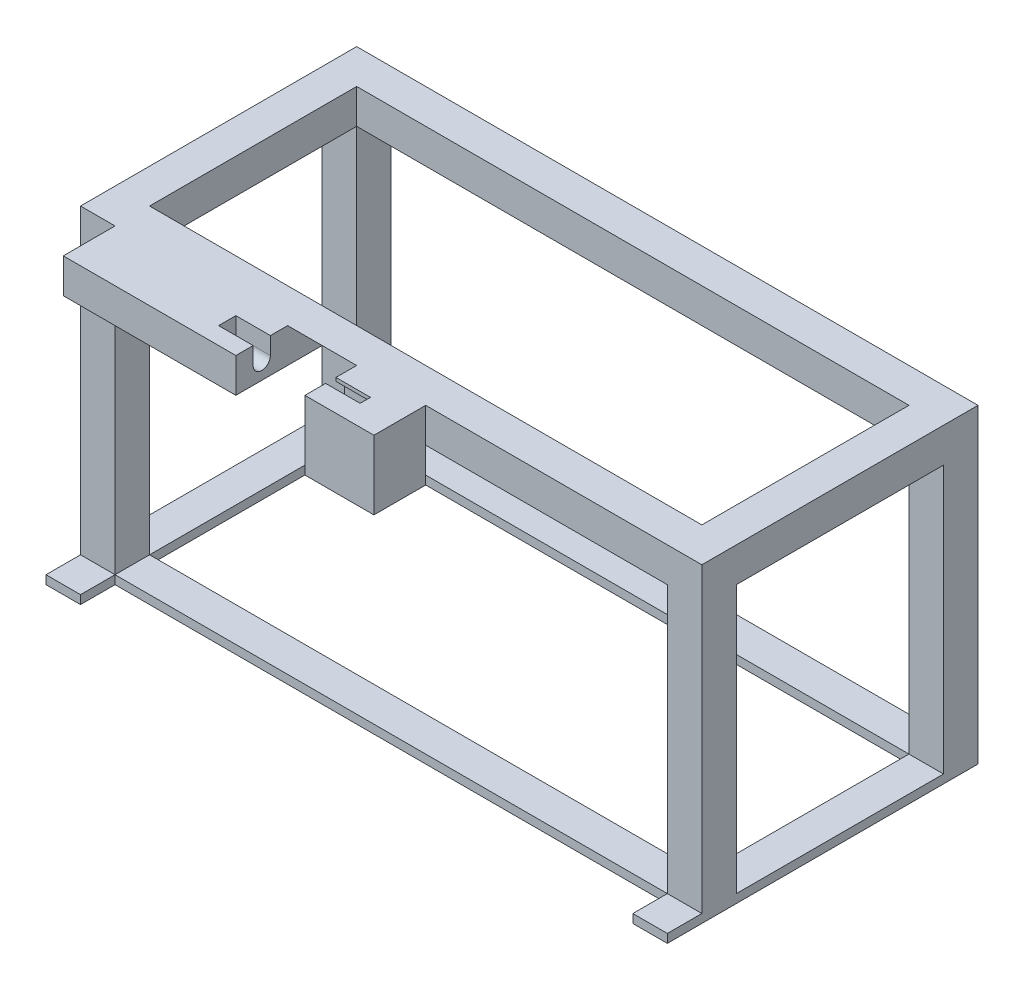
SolidWorks part; units mm, degrees
ref_plane "Front Plane" through (0, 0, 0) normal (0, 0, 1) x (1, 0, 0)
ref_plane "Top Plane" through (0, 0, 0) normal (0, 1, 0) x (1, 0, 0)
ref_plane "Right Plane" through (0, 0, 0) normal (1, 0, 0) x (0, 0, -1)
sketch "Sketch1" plane through (0, 0, 0) normal (0, 1, 0) x (1, 0, 0)
  line L0 (-203.2, 76.2) -> (-203.2, 101.6) construction
  line L1 (-203.2, -76.2) -> (203.2, -76.2)
  line L2 (-203.2, -76.2) -> (-203.2, 76.2)
  line L3 (-203.2, 76.2) -> (203.2, 76.2)
  line L4 (203.2, -76.2) -> (203.2, 76.2)
  line L5 (-203.2, -76.2) -> (203.2, 76.2) construction
  line L6 (-203.2, 76.2) -> (203.2, -76.2) construction
  line L7 (-228.6, -101.6) -> (228.6, -101.6)
  line L8 (-228.6, -101.6) -> (-228.6, 101.6)
  line L9 (-228.6, 101.6) -> (228.6, 101.6)
  line L10 (228.6, -101.6) -> (228.6, 101.6)
  line L11 (-228.6, -101.6) -> (228.6, 101.6) construction
  line L12 (-228.6, 101.6) -> (228.6, -101.6) construction
  line L13 (-203.2, 101.6) -> (-203.2, 76.2)
  line L14 (-203.2, 76.2) -> (-228.6, 76.2)
  line L15 (-228.6, -101.6) -> (-228.6, -127)
  line L16 (-228.6, -127) -> (-203.2, -127)
  line L17 (-203.2, -127) -> (-203.2, -101.6)
  line L18 (0, -125.73) -> (0, 125.73) construction
  line L19 (203.2, -127) -> (203.2, -101.6)
  line L20 (228.6, -127) -> (203.2, -127)
  line L21 (228.6, -101.6) -> (228.6, -127)
  line L22 (-203.2, -76.2) -> (-228.6, -76.2)
  line L23 (-203.2, -76.2) -> (-203.2, -101.6)
  line L24 (203.2, -76.2) -> (203.2, -101.6)
  line L25 (203.2, -76.2) -> (228.6, -76.2)
  line L26 (203.2, 76.2) -> (228.6, 76.2)
  line L27 (203.2, 101.6) -> (203.2, 76.2)
  point P0 (0, 0)
  point P6 (0, 0)
  dimension "D1" = 457.2
  dimension "D2" = 25.4
  dimension "D3" = 152.4
extrude "Boss-Extrude1" add sketch "Sketch1" along normal blind 6.35 separate body contours L23 L22 L8 L7 | L16 L17 L7 L15 | L24 L1 L23 L7 | L25 L24 L7 L10 | L21 L7 L19 L20 | L27 L9 L13 L3 | L22 L2 L14 L8 | L26 L4 L25 L10 region at (-215.9, 0, 0) region at (-215.9, 0, 88.9) region at (0, 0, 88.9) region at (215.9, 0, 88.9) region at (215.9, 0, 0) region at (0, 0, -88.9) region at (-215.9, 0, 114.3) region at (215.9, 0, 114.3)
extrude "Boss-Extrude2" add sketch "Sketch1<4>" along normal blind 228.6 contours L23 L22 L8 L7 | L25 L24 L7 L10 | L9 L27 L26 L10 | L14 L13 L9 L8 region at (-215.9, 0, 88.9) region at (215.9, 0, 88.9) region at (-215.9, 0, -88.9) region at (215.9, 0, -88.9)
sketch "Sketch1<4>" plane through (0, 0, 0) normal (0, 1, 0) x (1, 0, 0) same geometry as "Sketch1"
extrude "Boss-Extrude3" add sketch "Sketch1<5>" along normal blind 25.4 from offset 203.2 contours L27 L9 L13 L3 | L24 L1 L23 L7 | L22 L2 L14 L8 | L26 L4 L25 L10 region at (-215.9, 0, 0) region at (0, 0, 88.9) region at (215.9, 0, 0) region at (0, 0, -88.9)
sketch "Sketch1<5>" plane through (0, 0, 0) normal (0, 1, 0) x (1, 0, 0) same geometry as "Sketch1"
sketch "Sketch2" plane through (0, 0, 101.6) normal (0, 0, 1) x (1, 0, 0)
  line L0 (-203.2, 203.2) -> (-203.2, 228.6)
  line L1 (-228.6, 228.6) -> (228.6, 228.6) construction
  line L2 (-203.2, 203.2) -> (-76.2, 203.2)
  line L3 (-203.2, 203.2) -> (203.2, 203.2) construction
  line L4 (-76.2, 203.2) -> (-76.2, 228.6)
  line L5 (-76.2, 228.6) -> (-203.2, 228.6)
  line L6 (-25.4, 203.2) -> (-25.4, 228.6)
  line L7 (-25.4, 228.6) -> (25.4, 228.6)
  line L8 (25.4, 228.6) -> (25.4, 203.2)
  line L9 (25.4, 203.2) -> (-25.4, 203.2)
  dimension "D1" = 127
  dimension "D2" = 50.8
  dimension "D3" = 50.8
extrude "Boss-Extrude4" add sketch "Sketch2" along normal blind 38.1
sketch "Sketch3" plane through (-76.2, 0, 0) normal (1, 0, 0) x (0, 0, -1)
  line L0 (-139.7, 228.6) -> (-120.65, 215.9) construction
  line L1 (-120.65, 215.9) -> (-101.6, 228.6) construction
  line L2 (-120.65, 215.9) -> (-139.7, 203.2) construction
  line L3 (-120.65, 215.9) -> (-101.6, 203.2) construction
  point P1 (-120.65, 215.9)
  point P21 (-120.65, 215.9)
hole_wizard "1/2 (0.5) Diameter Hole1" positions "Sketch3" profile "Sketch4" hole size "1/2" standard "ANSI Inch"
sketch "Sketch4" plane through (-76.2, 215.9, 120.65) normal (0, 1, 0) x (0, 0, -1)
  line L0 (0, 0) -> (0, 25.4)
  line L1 (0, 25.4) -> (6.35, 25.4)
  line L2 (6.35, 25.4) -> (6.35, 0)
  line L5 (6.35, 0) -> (0, 0)
  line L10 (0, 25.4) -> (-6.35, 25.4) construction
  line L11 (0, -6.35) -> (0, 107.95) construction
  dimension "Hole Dia." = 12.7
  dimension "Hole Depth" = 25.4
sketch "Sketch5" plane through (0, 203.2, 0) normal (0, -1, 0) x (1, 0, 0)
  line L1 (-25.4, 101.6) -> (25.4, 101.6)
  line L2 (-25.4, 101.6) -> (-25.4, 139.7)
  line L3 (-25.4, 139.7) -> (25.4, 139.7)
  line L4 (25.4, 101.6) -> (25.4, 139.7)
extrude "Boss-Extrude5" add sketch "Sketch5" along normal blind 25.4
sketch "Sketch6" plane through (-25.4, 0, 0) normal (-1, 0, 0) x (0, 0, 1)
  line L0 (130.81, 226.06) -> (139.7, 226.06) construction
  line L1 (130.81, 226.06) -> (110.49, 226.06)
  line L2 (130.81, 226.06) -> (130.81, 185.928)
  line L3 (130.81, 185.928) -> (110.49, 185.928)
  line L4 (110.49, 226.06) -> (110.49, 185.928)
  line L5 (139.7, 228.6) -> (139.7, 203.2) construction
  line L6 (110.49, 226.06) -> (101.6, 226.06) construction
  line L7 (101.6, 228.6) -> (101.6, 6.35) construction
  dimension "D1" = 10.16
  dimension "D2" = 20.32
  dimension "D3" = 40.132
extrude "Cut-Extrude1" cut sketch "Sketch6" against normal blind 27.94
sketch "Sketch7" plane through (0, 228.6, 0) normal (0, 1, 0) x (1, 0, 0)
  line L0 (-76.2, -127) -> (-76.2, -114.3) construction
  line L1 (-76.2, -127) -> (-76.2, -114.3)
  line L2 (-76.2, -127) -> (-101.6, -127)
  line L3 (-101.6, -127) -> (-101.6, -120.65)
  line L4 (-101.6, -120.65) -> (-76.2, -120.65) construction
  line L5 (-101.6, -120.65) -> (-101.6, -114.3)
  line L6 (-101.6, -114.3) -> (-76.2, -114.3)
  dimension "D1" = 25.4
extrude "Cut-Extrude2" cut sketch "Sketch7" against normal blind 12.7
sketch "Sketch8" plane through (0, 228.6, 0) normal (0, 1, 0) x (1, 0, 0)
  line L0 (-25.4, -124.46) -> (0, -124.46)
  line L1 (-25.4, -139.7) -> (-25.4, -101.6) construction
  line L2 (-25.4, -120.65) -> (0, -120.65) construction
  line L4 (-25.4, -116.84) -> (0, -116.84)
  line L5 (0, -124.46) -> (0, -120.65)
  line L6 (0, -120.65) -> (0, -116.84)
  line L7 (-25.4, -124.46) -> (-25.4, -120.65)
  line L8 (-25.4, -120.65) -> (-25.4, -116.84)
  dimension "D1" = 7.62
  dimension "D2" = 25.4
extrude "Cut-Extrude3" cut sketch "Sketch8" against normal blind 12.7
sketch "Sketch9" plane through (-228.6, 0, 0) normal (-1, 0, 0) x (0, 0, 1)
  line L0 (76.2, 203.2) -> (101.6, 228.6)
  line L1 (101.6, 228.6) -> (101.6, 203.2)
  line L2 (101.6, 203.2) -> (76.2, 203.2)
  line L3 (76.2, 203.2) -> (76.2, 6.35) construction
  point P4 (76.2, 203.2)
  point P7 (0, 0)
  point P8 (79.1159, 203.2)
  point P9 (0, 0)
extrude "Cut-Extrude4" cut sketch "Sketch9" against normal up to surface (203.2 mm away) from surface up to face at (-25.4, 211.4843, 119.1846) starting at face at (-76.2, 218.2812, 120.65)
